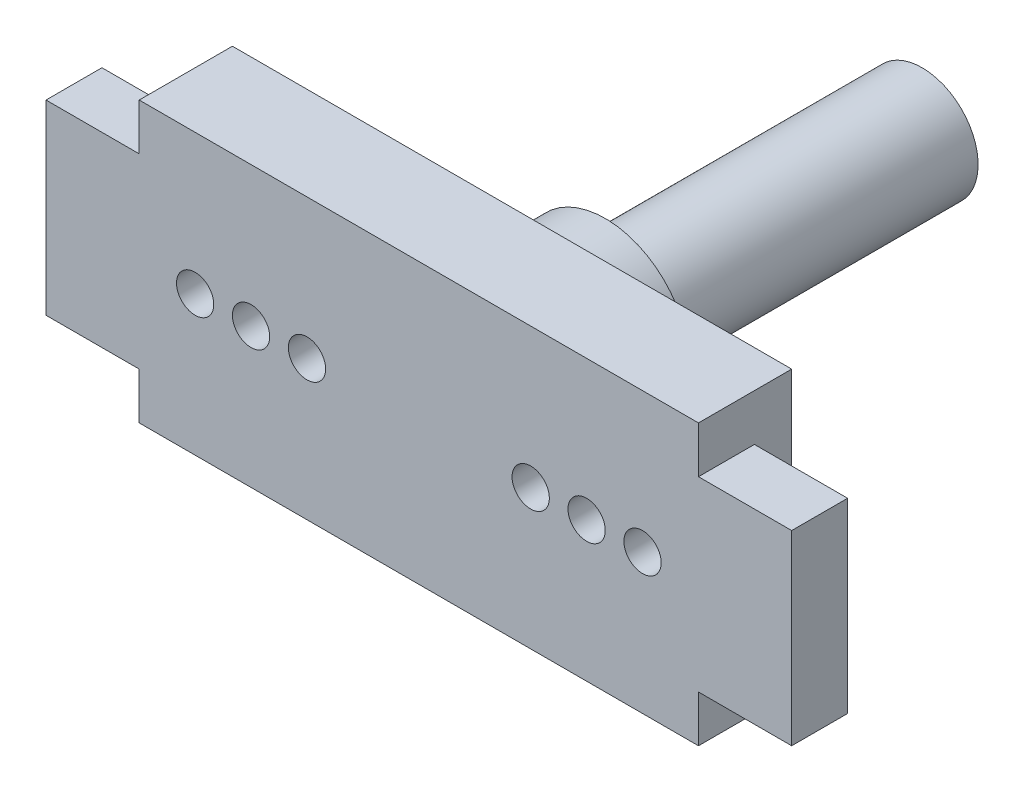
SolidWorks part; units mm, degrees
ref_plane "Front Plane" through (0, 0, 0) normal (0, 0, 1) x (1, 0, 0)
ref_plane "Top Plane" through (0, 0, 0) normal (0, 1, 0) x (1, 0, 0)
ref_plane "Right Plane" through (0, 0, 0) normal (1, 0, 0) x (0, 0, -1)
sketch "Sketch1" plane through (0, 0, 0) normal (0, 1, 0) x (1, 0, 0)
  line L1 (-61.8805, -26.2097) -> (-56.8805, -26.2097)
  line L2 (-61.8805, -26.2097) -> (-61.8805, 28.7903)
  line L3 (-61.8805, 28.7903) -> (-56.8805, 28.7903)
  line L4 (-56.8805, -26.2097) -> (-56.8805, 28.7903)
  line L5 (-56.8805, 28.7903) -> (-26.8805, 28.7903)
  line L6 (-56.8805, 28.7903) -> (-56.8805, 23.7903)
  line L7 (-56.8805, 23.7903) -> (-26.8805, 23.7903)
  line L8 (-26.8805, 28.7903) -> (-26.8805, 23.7903)
  line L9 (-26.8805, 28.7903) -> (-21.8805, 28.7903)
  line L10 (-26.8805, 28.7903) -> (-26.8805, -26.2097)
  line L11 (-26.8805, -26.2097) -> (-21.8805, -26.2097)
  line L12 (-21.8805, 28.7903) -> (-21.8805, -26.2097)
  dimension "D1" = 30
  dimension "D2" = 5
  dimension "D3" = 50
  dimension "D4" = 50
  dimension "D5" = 5
  dimension "D6" = 5
extrude "Boss-Extrude1" add sketch "Sketch1" along normal blind 15 contours L8 L5 L4 L7 region at (-41.8805, 0, -26.2903)
sketch "Sketch3" plane through (0, 0, -28.7903) normal (0, 0, -1) x (-1, 0, 0)
  line L0 (41.8805, 0) -> (41.8805, 15) construction
  line L1 (56.8805, 0) -> (26.8805, 0) construction
  line L2 (56.8805, 15) -> (26.8805, 15) construction
  circle A0 centre (35.8805, 7.5) radius 1
  circle A1 centre (32.8805, 7.5) radius 1
  circle A2 centre (29.8805, 7.5) radius 1
  circle A3 centre (53.8805, 7.5) radius 1
  circle A4 centre (50.8805, 7.5) radius 1
  circle A5 centre (47.8805, 7.5) radius 1
  dimension "D5" = 2
  dimension "D6" = 12
  dimension "D1" = 2
  dimension "D2" = 6
  dimension "D4" = 9
  dimension "D3" = 7.5
extrude "Cut-Extrude2" cut sketch "Sketch3" against normal up to surface (5 mm away) up to face at (-41.8805, 7.5, -23.7903)
sketch "Sketch4" plane through (0, 0, -28.7903) normal (0, 0, -1) x (-1, 0, 0)
  line L2 (56.8805, 0) -> (26.8805, 0) construction
  line L3 (26.8805, 15) -> (26.8805, 0) construction
  circle A0 centre (41.8805, 7.5) radius 3
  dimension "D3" = 6
  dimension "D1" = 7.5
  dimension "D2" = 15
sketch "Sketch5" plane through (0, 0, -23.7903) normal (0, 0, 1) x (1, 0, 0)
  line L0 (-56.8805, 15) -> (-56.8805, 0) construction
  line L1 (-56.8805, 12.5) -> (-61.8805, 12.5)
  line L2 (-56.8805, 12.5) -> (-56.8805, 2.5)
  line L3 (-56.8805, 2.5) -> (-61.8805, 2.5)
  line L4 (-61.8805, 12.5) -> (-61.8805, 2.5)
  line L5 (-56.8805, 15) -> (-26.8805, 15) construction
  line L6 (-56.8805, 0) -> (-26.8805, 0) construction
  line L7 (-41.8805, 15) -> (-41.8805, 0) construction
  line L8 (-26.8805, 2.5) -> (-21.8805, 2.5)
  line L9 (-21.8805, 12.5) -> (-21.8805, 2.5)
  line L10 (-26.8805, 12.5) -> (-21.8805, 12.5)
  line L11 (-26.8805, 12.5) -> (-26.8805, 2.5)
  dimension "D1" = 2.5
  dimension "D2" = 2.5
  dimension "D3" = 5
extrude "Boss-Extrude2" add sketch "Sketch5" against normal blind 3 contours L2 L1 L4 L3 | L8 L9 L10 L11
extrude "Boss-Extrude3" add sketch "Sketch4" along normal blind 22
sketch "Sketch6" plane through (0, 0, -28.7903) normal (0, 0, -1) x (-1, 0, 0)
  circle A0 centre (41.8805, 7.5) radius 3
  circle A1 centre (41.8805, 7.5) radius 4.5
extrude "Boss-Extrude4" add sketch "Sketch6" along normal blind 5
